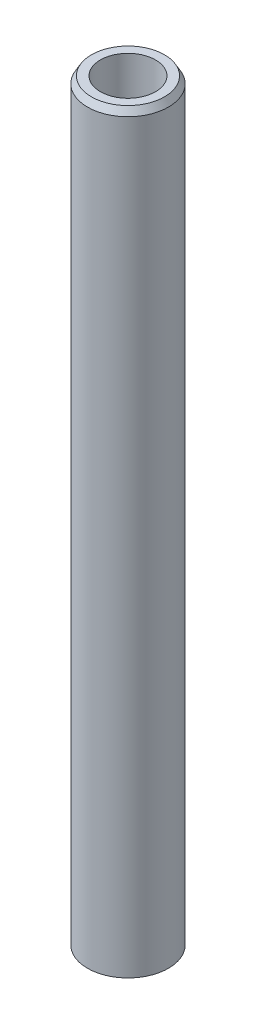
SolidWorks part; units mm, degrees
ref_plane "Front Plane" through (0, 0, 0) normal (0, 0, 1) x (1, 0, 0)
ref_plane "Top Plane" through (0, 0, 0) normal (0, 1, 0) x (1, 0, 0)
ref_plane "Right Plane" through (0, 0, 0) normal (1, 0, 0) x (0, 0, -1)
sketch "Sketch1" plane through (0, 0, 0) normal (0, 1, 0) x (1, 0, 0)
  circle A0 centre (0, 0) radius 30
  dimension "SHAFT_OD" = 60
extrude "Boss-Extrude1" add sketch "Sketch1" along normal blind 561.0148
sketch "Sketch2" plane through (0, 0, 0) normal (0, 1, 0) x (1, 0, 0)
  circle A0 centre (0, 0) radius 20.4446
  dimension "BORE_D" = 40.8891
extrude "Cut-Extrude1" cut sketch "Sketch2" along normal through all
chamfer "Chamfer1" distance 5.0968 angle 30 2 edges at (0, 561.0148, 30) (0, 0, 30) first distance on face at (0, 561.0148, 30) first distance on face at (0, 0, 20.4446)
